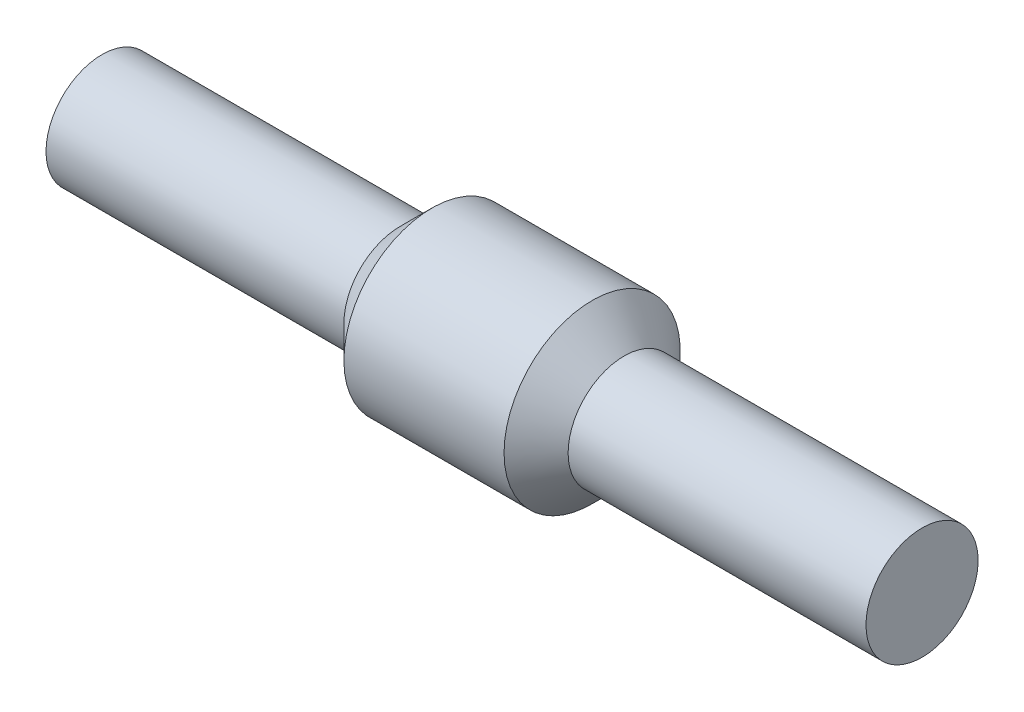
SolidWorks part; units mm, degrees
ref_plane "Front Plane" through (0, 0, 0) normal (0, 0, 1) x (1, 0, 0)
ref_plane "Top Plane" through (0, 0, 0) normal (0, 1, 0) x (1, 0, 0)
ref_plane "Right Plane" through (0, 0, 0) normal (1, 0, 0) x (0, 0, -1)
sketch "Sketch1" plane through (0, 0, 0) normal (0, 0, 1) x (1, 0, 0)
  line L0 (-20, 0) -> (20, 0) construction
  dimension "D1" = 40
sketch "Sketch2" plane through (0, 0, 0) normal (0, 0, 1) x (1, 0, 0)
  line L0 (12.8, 0) -> (12.8, 1.75)
  line L1 (-20, 0) -> (20, 0) construction
  line L2 (12.8, 1.75) -> (3.5, 1.75)
  line L3 (3.5, 1.75) -> (2.5, 2.75)
  line L4 (2.5, 2.75) -> (0, 2.75)
  line L5 (0, 2.75) -> (0, 0)
  line L6 (0, 0) -> (12.8, 0)
  dimension "D1" = 10.3
  dimension "D2" = 2.75
  dimension "D3" = 1
  dimension "D4" = 7.2
  dimension "D5" = 45
revolve "Revolve1" add sketch "Sketch2" angle 360 about L0
mirror "Mirror1" about plane through (0, 0, 0) normal (1, 0, 0) of "Revolve1"
move or copy body "Body-Move/Copy1" [suppressed] bodies to move or copy 102
move or copy body "Body-Move/Copy2" [suppressed] bodies to move or copy 102
equation "\"end to end\"= 40"
equation "\"D1@Sketch1\"=\"end to end\""
